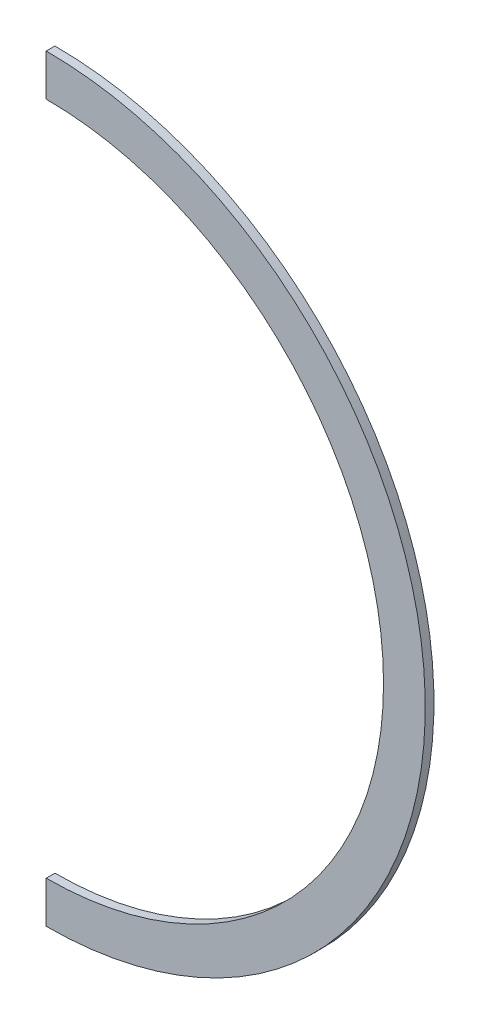
SolidWorks part; units mm, degrees
material "Balsa"
ref_plane "Front Plane" through (0, 0, 0) normal (0, 0, 1) x (1, 0, 0)
ref_plane "Top Plane" through (0, 0, 0) normal (0, 1, 0) x (1, 0, 0)
ref_plane "Right Plane" through (0, 0, 0) normal (1, 0, 0) x (0, 0, -1)
sketch "Sketch1" plane through (0, 0, 0) normal (0, 0, 1) x (1, 0, 0)
  line L0 (0, 32.094) -> (0, -346.2619) construction
  line L1 (0, 0) -> (0, 244.345) construction
  line L2 (0, 0) -> (0, 471.6969) construction
  line L3 (0, 0) -> (-283.5939, 0) construction
  line L4 (-127.2933, -32.5553) -> (-85.9841, -73.8644)
  line L5 (-85.9841, -73.8644) -> (-85.9841, -86.6438)
  line L6 (-85.9841, -73.8644) -> (-54.3993, -105.4493) construction
  arc A0 (-54.3993, -105.4493) -> (-127.2933, -32.5553) centre (0, 21.844) ccw
  arc A2 (-82.075, -89.6305) -> (-54.3993, -105.4493) centre (0, 21.844) ccw construction
  arc A3 (-127.2933, -32.5553) -> (-82.075, -89.6305) centre (0, 21.844) ccw construction
  arc A4 (-85.9841, -86.6438) -> (-54.3993, -105.4493) centre (0, 21.844) ccw
  spline S2 degree 3 poles (-19.218, -1838.2141) (276.9397, -392.4777) (232.9593, 72.7514) (49.9381, 150.9258) (45.7097, 152.4909) (37.1079, 155.2035) (32.7346, 156.3511) (27.1752, 157.5183) (26.0587, 157.7384) (23.8163, 158.1514) (22.6888, 158.3447) (19.306, 158.8811) (17.0511, 159.1813) (10.2867, 159.9126) (1.2693, 160.4377) (-7.745, 160.0789) (-14.5046, 159.4749) (-16.7575, 159.2176) (-20.1367, 158.7464) (-21.263, 158.5751) (-23.5156, 158.2037) (-24.6421, 158.0036) (-30.2426, 156.9366) (-34.6466, 155.8674) (-43.3063, 153.3113) (-47.562, 151.8242) (-55.9254, 148.4331) (-60.0331, 146.529) (-66.0807, 143.3516) (-68.0818, 142.2359) (-72.0044, 139.9197) (-73.9301, 138.7173) (-79.6017, 134.9792) (-86.884, 129.6473) (-93.6143, 123.6295) (-98.4521, 118.8554) (-100.0296, 117.2204) (-102.3424, 114.7015) (-103.1054, 113.8496) (-104.6077, 112.1297) (-105.3467, 111.2623) (-108.9818, 106.8875) (-111.6981, 103.2683) (-116.7574, 95.7975) (-119.1004, 91.9459) (-123.4121, 84.0098) (-125.3809, 79.9253) (-127.6006, 74.6695) (-128.0327, 73.61) (-128.8681, 71.4874) (-129.2719, 70.423) (-130.4422, 67.2205) (-131.1674, 65.0732) (-133.1812, 58.5951) (-135.4347, 49.861) (-136.834, 40.9354) (-137.5569, 34.168) (-137.7434, 31.9) (-137.9397, 28.4793) (-137.9911, 27.3374) (-138.0656, 25.0596) (-138.0887, 23.9223) (-138.135, 18.2442) (-137.9496, 13.7276) (-137.1441, 4.7454) (-136.5239, 0.2797) (-134.8456, -8.6005) (-133.7876, -13.015) (-131.2181, -21.791) (-129.7278, -26.0794) (-126.351, -34.4622) (-124.4643, -38.5569) (-120.2966, -46.5538) (-118.0156, -50.456) (-114.9122, -55.2108) (-114.2789, -56.1556) (-112.9868, -58.0327) (-112.3272, -58.9661) (-110.315, -61.7398) (-108.9333, -63.5482) (-104.6702, -68.8537) (-98.6716, -75.6089) (-92.0553, -81.7381) (-86.8592, -86.0978) (-85.0881, -87.5114) (-82.3719, -89.5716) (-81.4566, -90.2482) (-79.6058, -91.5811) (-78.6696, -92.238) (117.1329, -226.0075) (630.1685, 154.3992) (1500.4507, 1111.3958) knots -1.313799 -1.313799 -1.313799 -1.313799 0.03125 0.03125 0.0625 0.0625 0.09375 0.09375 0.101563 0.101563 0.109375 0.109375 0.125 0.125 0.15625 0.1875 0.1875 0.203125 0.203125 0.210937 0.210937 0.21875 0.21875 0.25 0.25 0.28125 0.28125 0.3125 0.3125 0.328125 0.328125 0.34375 0.34375 0.375 0.40625 0.40625 0.421875 0.421875 0.429687 0.429687 0.4375 0.4375 0.46875 0.46875 0.5 0.5 0.53125 0.53125 0.539062 0.539062 0.546875 0.546875 0.5625 0.5625 0.59375 0.625 0.625 0.640625 0.640625 0.648437 0.648437 0.65625 0.65625 0.6875 0.6875 0.71875 0.71875 0.75 0.75 0.78125 0.78125 0.8125 0.8125 0.84375 0.84375 0.851562 0.851562 0.859375 0.859375 0.875 0.875 0.90625 0.9375 0.9375 0.953125 0.953125 0.960937 0.960937 0.96875 0.96875 2.582348 2.582348 2.582348 2.582348 only from (66.3397, 143.1887) to (-66.0465, -100.0388)
  spline S3 degree 3 poles (66.3397, 143.1887) (62.3323, 145.3909) (58.2494, 147.3758) (49.9381, 150.9258) (45.7097, 152.4909) (37.1079, 155.2035) (32.7346, 156.3511) (27.1752, 157.5183) (26.0587, 157.7384) (23.8163, 158.1514) (22.6888, 158.3447) (19.306, 158.8811) (17.0511, 159.1813) (10.2867, 159.9126) (1.2693, 160.4377) (-7.745, 160.0789) (-14.5046, 159.4749) (-16.7575, 159.2176) (-20.1367, 158.7464) (-21.263, 158.5751) (-23.5156, 158.2037) (-24.6421, 158.0036) (-30.2426, 156.9366) (-34.6466, 155.8674) (-43.3063, 153.3113) (-47.562, 151.8242) (-55.9254, 148.4331) (-60.0331, 146.529) (-66.0807, 143.3516) (-68.0818, 142.2359) (-72.0044, 139.9197) (-73.9301, 138.7173) (-79.6017, 134.9792) (-86.884, 129.6473) (-93.6143, 123.6295) (-98.4521, 118.8554) (-100.0296, 117.2204) (-102.3424, 114.7015) (-103.1054, 113.8496) (-104.6077, 112.1297) (-105.3467, 111.2623) (-108.9818, 106.8875) (-111.6981, 103.2683) (-116.7574, 95.7975) (-119.1004, 91.9459) (-123.4121, 84.0098) (-125.3809, 79.9253) (-127.6006, 74.6695) (-128.0327, 73.61) (-128.8681, 71.4874) (-129.2719, 70.423) (-130.4422, 67.2205) (-131.1674, 65.0732) (-133.1812, 58.5951) (-135.4347, 49.861) (-136.834, 40.9354) (-137.5569, 34.168) (-137.7434, 31.9) (-137.9397, 28.4793) (-137.9911, 27.3374) (-138.0656, 25.0596) (-138.0887, 23.9223) (-138.135, 18.2442) (-137.9496, 13.7276) (-137.1441, 4.7454) (-136.5239, 0.2797) (-134.8456, -8.6005) (-133.7876, -13.015) (-131.2181, -21.791) (-129.7278, -26.0794) (-127.6847, -31.1513) (-127.3213, -32.0275) (-126.9491, -32.8995) knots 0 0 0 0 0.03125 0.03125 0.0625 0.0625 0.09375 0.09375 0.101563 0.101563 0.109375 0.109375 0.125 0.125 0.15625 0.1875 0.1875 0.203125 0.203125 0.210937 0.210937 0.21875 0.21875 0.25 0.25 0.28125 0.28125 0.3125 0.3125 0.328125 0.328125 0.34375 0.34375 0.375 0.40625 0.40625 0.421875 0.421875 0.429687 0.429687 0.4375 0.4375 0.46875 0.46875 0.5 0.5 0.53125 0.53125 0.539062 0.539062 0.546875 0.546875 0.5625 0.5625 0.59375 0.625 0.625 0.640625 0.640625 0.648437 0.648437 0.65625 0.65625 0.6875 0.6875 0.71875 0.71875 0.75 0.75 0.78125 0.78125 0.787815 0.787815 0.787815 0.787815 construction
  point P2 (0, 160.2226)
  point P3 (0, -116.9127)
  point P23 (-85.9841, -73.8644)
  dimension "D1" = 277.1353
  dimension "D2" = 276.86
  dimension "D3" = 21.844
  dimension "D5" = 45
  dimension "D6" = 113.03
  dimension "D4" = 58.42
  dimension "D7" = 45
extrude "Boss-Extrude1" add sketch "Sketch1" along normal mid plane 3.175
sketch "Sketch2" plane through (0, 0, 1.5875) normal (0, 0, 1) x (1, 0, 0)
  line L4 (-114.3729, -23.9231) -> (-70.7441, -67.5518)
  line L5 (-70.7441, -67.5518) -> (-70.7441, -79.0076)
  line L6 (-114.3729, -23.9231) -> (-70.7441, -67.5518)
  line L7 (-70.7441, -67.5518) -> (-70.7441, -79.0076)
  arc A2 (-70.7441, -79.0076) -> (-114.3729, -23.9231) centre (0, 21.844) ccw
  arc A3 (-70.7441, -79.0076) -> (-114.3729, -23.9231) centre (0, 21.844) ccw
  dimension "D1" = 15.24
extrude "Cut-Extrude1" cut sketch "Sketch2" against normal up to surface (3.175 mm away) up to face at (-27.5361, -9.1994, -1.5875)
fillet "Fillet1" radius 8.89 6 edges at (-127.2933, -32.5553, 0) (-114.3729, -23.9231, 0) (-85.9841, -73.8644, 0) (-85.9841, -86.6438, 0) (-70.7441, -67.5518, 0) (-70.7441, -79.0076, 0)
sketch "Sketch3" plane through (0, 0, 1.5875) normal (0, 0, 1) x (1, 0, 0)
  line L0 (0, 49.992) -> (0, 733.2) construction
  line L1 (0, 49.992) -> (0, 733.2) construction
  line L2 (-136.2041, -28.3557) -> (0, 49.992) construction
  line L3 (136.2041, -28.3557) -> (0, 49.992) construction
  line L4 (-136.2041, -28.3557) -> (0, 49.992) construction
  line L5 (136.2041, -28.3557) -> (0, 49.992) construction
  line L6 (-1.651, 152.6442) -> (-1.651, 160.2642)
  line L7 (1.651, 152.6442) -> (1.651, 160.2642)
  line L8 (-1.651, 152.6442) -> (1.651, 152.6442)
  line L9 (119.8454, -45.9681) -> (106.751, -38.3801)
  line L10 (121.4405, -43.2127) -> (108.3453, -35.6242)
  line L11 (-126.0584, -33.7901) -> (-88.588, -71.2606)
  line L12 (-85.9841, -77.5468) -> (-85.9841, -82.2574)
  line L13 (-126.0584, -33.7901) -> (-88.588, -71.2606) construction
  line L14 (-85.9841, -77.5468) -> (-85.9841, -82.2574) construction
  line L18 (121.4405, -43.2127) -> (108.3453, -35.6242)
  line L30 (-123.167, -47.8929) -> (-104.8699, -37.29)
  line L35 (119.8454, -45.9681) -> (106.751, -38.3801)
  line L47 (108.5244, -35.721) -> (120.1169, -46.1175) construction
  line L48 (114.3206, -40.9193) -> (126.5619, -48.0121) construction
  line L49 (113.8577, -42.5592) -> (122.0137, -47.2849)
  line L50 (115.5132, -39.7021) -> (123.6691, -44.4278)
  line L51 (113.8577, -42.5592) -> (115.5132, -39.7021)
  line L52 (122.0137, -47.2849) -> (123.6691, -44.4278)
  line L58 (-124.7703, -45.1423) -> (-106.4658, -34.5351)
  line L59 (-124.7703, -45.1423) -> (-123.167, -47.8929)
  line L71 (-124.7703, -45.1423) -> (-123.167, -47.8929) construction
  line L72 (-124.7703, -45.1423) -> (-106.4658, -34.5351) construction
  line L73 (-123.167, -47.8929) -> (-104.8699, -37.29) construction
  line L74 (-123.167, -47.8929) -> (-107.9499, -35.3951) construction
  line L75 (-115.5584, -41.644) -> (-110.9064, -38.9482) construction
  line L76 (-119.3826, -41.9518) -> (-112.6266, -38.0369)
  line L77 (-117.727, -44.8088) -> (-110.971, -40.8938)
  line L78 (-119.3826, -41.9518) -> (-117.727, -44.8088)
  line L79 (-112.6266, -38.0369) -> (-110.971, -40.8938)
  arc A0 (-54.3993, -105.4493) -> (-127.2933, -32.5553) centre (0, 21.844) ccw construction
  arc A2 (-1.651, 160.2642) -> (-130.2816, -24.9489) centre (0, 21.844) ccw construction
  arc A3 (-130.2816, -24.9489) -> (-127.2933, -32.5553) centre (0, 21.844) ccw construction
  arc A4 (-1.651, 160.2642) -> (-130.2816, -24.9489) centre (0, 21.844) ccw construction
  arc A5 (-130.2816, -24.9489) -> (-127.9919, -30.8906) centre (0, 21.844) ccw construction
  arc A6 (-82.3849, -89.4016) -> (-127.9919, -30.8906) centre (0, 21.844) ccw
  arc A7 (-127.9919, -30.8906) -> (-126.0584, -33.7901) centre (-119.7722, -27.504) ccw
  arc A8 (-85.9841, -77.5468) -> (-88.588, -71.2606) centre (-94.8741, -77.5468) ccw
  arc A9 (-85.9841, -82.2574) -> (-82.3849, -89.4016) centre (-77.0941, -82.2574) ccw
  arc A11 (-127.9919, -30.8906) -> (-126.0584, -33.7901) centre (-119.7722, -27.504) ccw construction
  arc A12 (-85.9841, -77.5468) -> (-88.588, -71.2606) centre (-94.8741, -77.5468) ccw construction
  arc A13 (-85.9841, -82.2574) -> (-82.3849, -89.4016) centre (-77.0941, -82.2574) ccw construction
  arc A14 (130.2816, -24.9489) -> (1.651, 160.2642) centre (0, 21.844) ccw construction
  arc A15 (1.651, 160.2642) -> (-1.651, 160.2642) centre (0, 21.844) ccw
  arc A16 (130.2816, -24.9489) -> (1.651, 160.2642) centre (0, 21.844) ccw construction
  arc A17 (1.651, 160.2642) -> (-1.651, 160.2642) centre (0, 21.844) ccw
  spline S0 degree 3 poles (106.751, -38.3801) (107.2824, -37.4615) (107.8139, -36.5429) (108.3453, -35.6242) knots 0 0 0 0 1 1 1 1 weights 1 1 1 1
  spline S1 degree 3 poles (119.8454, -45.9681) (120.3771, -45.0496) (120.9088, -44.1312) (121.4405, -43.2127) knots 0 0 0 0 1 1 1 1 weights 1 1 1 1
  spline S2 degree 3 poles (-885.9995, -1769.7517) (-211.5636, -622.9991) (457.4593, 532.6423) (1115.3786, 1687.3419) knots -628.025775 -628.025775 -628.025775 -628.025775 629.321979 629.321979 629.321979 629.321979 weights 1.00213 0.999289 0.99929 1.002132 only from (119.8454, -45.9681) to (121.4405, -43.2127)
  spline S3 degree 3 poles (-1102.9627, 1696.4309) (-441.8958, 540.8878) (227.2797, -614.2574) (901.0153, -1762.8792) knots -628.210418 -628.210418 -628.210418 -628.210418 629.142066 629.142066 629.142066 629.142066 weights 1.001328 0.999558 0.999557 1.001327 only from (-106.4658, -34.5351) to (-104.8699, -37.29)
  spline S4 degree 3 poles (-106.4658, -34.5351) (-105.9338, -35.4534) (-105.4019, -36.3717) (-104.8699, -37.29) knots 0 0 0 0 1 1 1 1 weights 1 1 1 1 construction
  spline S6 degree 3 poles (-898.4881, -1762.9922) (-224.3422, -615.0331) (444.2887, 540.7283) (1102.2727, 1695.4213) knots -627.922306 -627.922306 -627.922306 -627.922306 629.42597 629.42597 629.42597 629.42597 weights 1.001921 0.999359 0.99936 1.001924 only from (106.751, -38.3801) to (108.3453, -35.6242)
  point P49 (-116.0256, -43.8229)
  point P50 (120.451, -46.3794)
  arc M19 (-82.3849, -89.4016) -> (-127.9919, -30.8906) centre (0, 21.844) ccw
  line M21 (-126.0584, -33.7901) -> (-88.588, -71.2606)
  dimension "D1" = 3.302
  dimension "D2" = 7.62
  dimension "D4" = 3.302
  dimension "D5" = 7.62
  dimension "D6" = 3.302
  dimension "D7" = 5.842
  dimension "D3" = 0
extrude "Cut-Extrude2" [suppressed] cut sketch "Sketch3" against normal through all contours L79 L76 L77 M21 | L6 L8 L7 M19 | L51 L49 L50 M19
sketch "Sketch4" plane through (0, 0, 0) normal (1, 0, 0) x (0, 0, -1)
  line L1 (-96.2805, 232.7957) -> (122.2438, 232.7957)
  line L2 (-96.2805, 232.7957) -> (-96.2805, -207.8589)
  line L3 (-96.2805, -207.8589) -> (122.2438, -207.8589)
  line L4 (122.2438, 232.7957) -> (122.2438, -207.8589)
extrude "Cut-Extrude3" cut sketch "Sketch4" against normal through all
equation "\"a\"= 0.06"
equation "\"slotwidth\"=0.13"
equation "\"slotheight\"=0.3"
